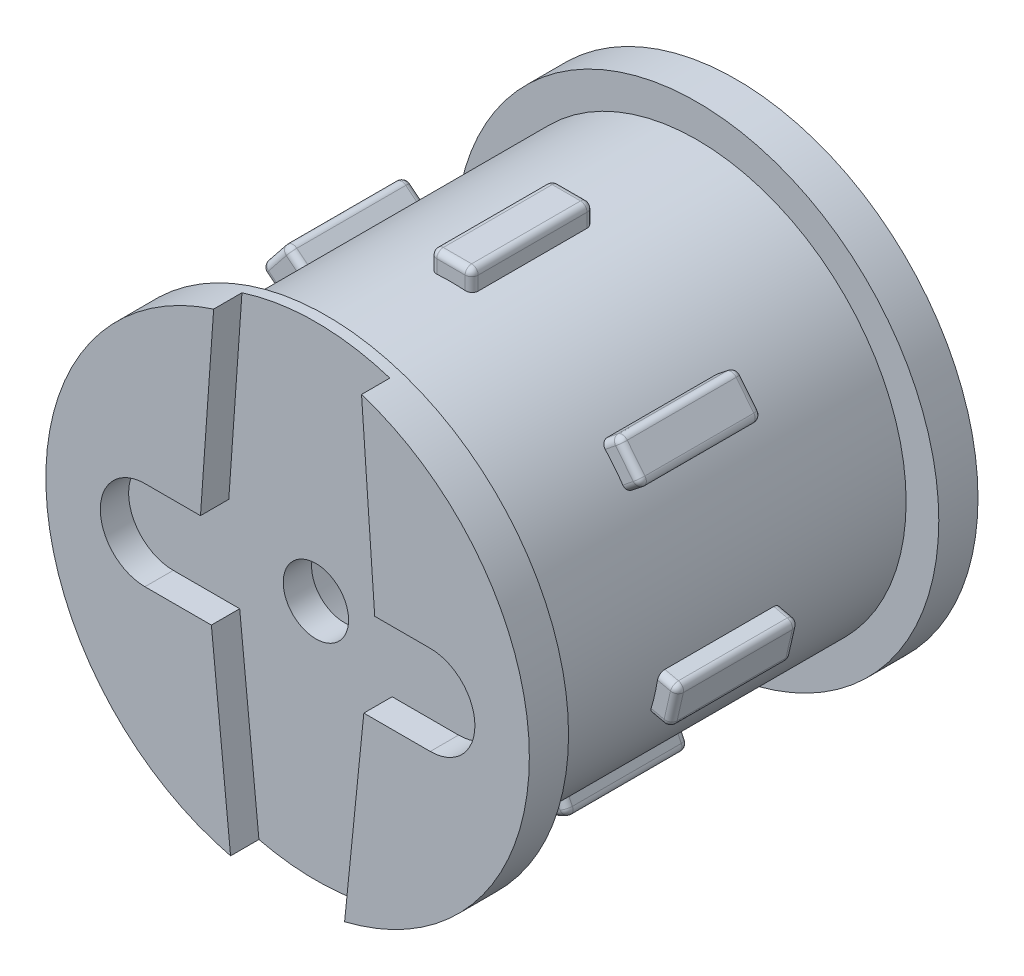
SolidWorks part; units mm, degrees
ref_plane "Ebene vorne" through (0, 0, 0) normal (0, 0, 1) x (1, 0, 0)
ref_plane "Ebene oben" through (0, 0, 0) normal (0, 1, 0) x (1, 0, 0)
ref_plane "Ebene rechts" through (0, 0, 0) normal (1, 0, 0) x (0, 0, -1)
sketch "Skizze1" plane through (0, 0, 0) normal (0, 0, 1) x (1, 0, 0)
  circle A0 centre (0, 0) radius 9.6
  dimension "D1" = 19.2
extrude "Aufsatz-Linear austragen1" add sketch "Skizze1" along normal blind 10.3 and the other way blind 10.3
ref_axis "Rotationsachse" through (0, 0, -10.3) along (0, 0, 1)
sketch "Skizze2" plane through (0, 0, 10.3) normal (0, 0, 1) x (1, 0, 0)
  circle A0 centre (0, 0) radius 11.1
  dimension "D1" = 22.2
extrude "Aufsatz-Linear austragen2" add sketch "Skizze2" against normal blind 1.8
sketch "Skizze3" plane through (0, 0, -10.3) normal (0, 0, -1) x (-1, 0, 0)
  circle A0 centre (0, 0) radius 11.1
  dimension "D1" = 22.2
extrude "Aufsatz-Linear austragen3" add sketch "Skizze3" against normal blind 1.8
sketch "Skizze12" plane through (0, 0, 10.3) normal (0, 0, 1) x (1, 0, 0)
  line L0 (1.9899, -17.001) -> (3.5, -2.05)
  line L1 (-3.05, 2.05) -> (3.05, 2.05)
  line L2 (-3.05, 2.05) -> (-3.05, -2.05)
  line L3 (-3.05, -2.05) -> (3.05, -2.05)
  line L4 (3.05, 2.05) -> (3.05, -2.05)
  line L5 (-3.05, 2.05) -> (3.05, -2.05) construction
  line L6 (-3.05, -2.05) -> (3.05, 2.05) construction
  line L7 (3.05, 2.05) -> (6.55, 2.05)
  line L8 (3.05, 2.05) -> (3.05, -2.05)
  line L9 (3.05, -2.05) -> (6.55, -2.05)
  line L10 (6.55, 2.05) -> (6.55, -2.05)
  line L11 (-3.05, -2.05) -> (-3.5, -2.05)
  line L12 (-1.9899, -17.001) -> (-3.5, -2.05)
  line L13 (4, 2.05) -> (2.7431, 19.7448)
  line L14 (-4, 2.05) -> (-2.7431, 19.7448)
  line L16 (-3.05, -2.05) -> (-6.55, -2.05)
  line L17 (-3.05, -2.05) -> (-3.05, 2.05)
  line L18 (-3.05, 2.05) -> (-6.55, 2.05)
  line L19 (-6.55, -2.05) -> (-6.55, 2.05)
  circle A0 centre (6.55, 0) radius 2.05
  circle A1 centre (0, -16.8) radius 2
  circle A2 centre (0, 19.55) radius 2.75
  circle A3 centre (-6.55, 0) radius 2.05
  point P0 (0, 0)
  point P12 (0, -2.05)
  circle M11 centre (0, 0) radius 11.1
  dimension "D5" = 4
  dimension "D9" = 17.5
  dimension "D13" = 5.5
  dimension "D6" = 4.1
  dimension "D2" = 4.1
  dimension "D1" = 6.1
  dimension "D3" = 3.5
  dimension "D4" = 14.75
  dimension "D7" = 3.5
  dimension "D8" = 3.5
  dimension "D10" = 4
  dimension "D11" = 4
  dimension "D12" = 3.5
extrude "Schnitt-Linear austragen1" cut sketch "Skizze12" against normal blind 1.3 contours A1 M11 | L11 L9 L3 M11 | L4 L1 L2 L3 | A0 L7 L4 L9 | L10 A0 | L10 A0 | L18 L1 L7 L13 L14 M11 | A2 L14 L13 M11 | L17 L16 L19 L18 | A3 | A2 | L2 L1 L4 L3 region at (0, -13.1061, 10.3) region at (0, -6.3029, 10.3) region at (4.0504, 0, 10.3) region at (0, 0, 10.3) region at (5.68, 0, 10.3) region at (7.42, 0, 10.3) region at (0, 6.3626, 10.3) region at (0, 14.1384, 10.3)
sketch "Skizze8" plane through (0, 0, 0) normal (1, 0, 0) x (0, 0, -1)
  line L0 (10.3, 0) -> (10.3, 8)
  line L1 (10.3, -11.1) -> (10.3, 11.1) construction
  line L2 (10.3, 8) -> (8.5, 8)
  line L3 (8.5, 11.1) -> (8.5, -11.1) construction
  line L4 (8.5, 8) -> (-7.7, 3.5)
  line L6 (-7.7, 3.5) -> (-7.7, 0)
  line L7 (-7.7, 0) -> (10.3, 0)
  dimension "D1" = 8
  dimension "D2" = 3.5
  dimension "D3" = 18
revolve "Schnitt-Rotation1" cut sketch "Skizze8" angle 360 about axis through (0, 0, -10.3) along (0, 0, 1)
ref_plane "Schnittebene_Zaehne" through (0, 0, 0) normal (0, 0, -1) x (-1, 0, 0)
sketch "Skizze11" plane through (0, 0, 0) normal (0, 0, -1) x (-1, 0, 0)
  line L0 (0, 0) -> (0, 12.664) construction
  line L6 (-0.95, 8.71) -> (0.95, 8.71)
  line L7 (-0.95, 8.71) -> (-0.95, 10.49)
  line L8 (-0.95, 10.49) -> (0.95, 10.49)
  line L9 (0.95, 8.71) -> (0.95, 10.49)
  line L10 (-0.95, 8.71) -> (0.95, 10.49) construction
  line L11 (-0.95, 10.49) -> (0.95, 8.71) construction
  circle A1 centre (0, 0) radius 9.6 construction
  point P3 (0, 9.6)
  dimension "D1" = 0.89
  dimension "D2" = 1.9
extrude "Aufsatz-Linear austragen4" add sketch "Skizze11" along normal blind 2.8 and the other way blind 2.8
pattern_circular "Kreismuster2" count 7 over 360 about axis through (0, 0, -10.3) along (0, 0, 1) of "Aufsatz-Linear austragen4"
fillet "Verrundung1" radius 0.3 56 edges at (8.2014, 6.5404, 2.8) (7.6091, 7.2831, 0) (8.2014, 6.5404, -2.8) (8.7937, 5.7977, 0) (-8.4274, 5.5055, 2.8) (-7.2428, 6.991, 2.8) (-7.2428, 6.991, -2.8) (-8.4274, 5.5055, -2.8) (-9.5588, -3.1562, -2.8) (-9.9816, -1.3038, -2.8) (-9.5588, -3.1562, 2.8) (-9.9816, -1.3038, 2.8) (-5.2041, -8.6168, -2.8) (-3.4922, -9.4412, -2.8) (-3.4922, -9.4412, 2.8) (-5.2041, -8.6168, 2.8) (5.2041, -8.6168, 2.8) (3.4922, -9.4412, 2.8) (3.4922, -9.4412, -2.8) (5.2041, -8.6168, -2.8) (9.5588, -3.1562, 2.8) (9.5588, -3.1562, -2.8) (9.9816, -1.3038, 2.8) (9.9816, -1.3038, -2.8) (8.4274, 5.5055, 2.8) (8.4274, 5.5055, -2.8) (7.2428, 6.991, -2.8) (7.2428, 6.991, 2.8) (0.95, 10.0214, 2.8) (0.95, 10.0214, -2.8) (-0.95, 10.0214, -2.8) (-0.95, 10.0214, 2.8) (10.4384, -1.4081, 0) (10.227, -2.3342, 2.8) (10.227, -2.3342, -2.8) (10.0156, -3.2604, 0) (4.5514, -9.4512, 2.8) (4.5514, -9.4512, -2.8) (5.4074, -9.039, 0) (3.6955, -9.8634, 0) (-4.5514, -9.4512, 2.8) (-4.5514, -9.4512, -2.8) (-5.4074, -9.039, 0) (-3.6955, -9.8634, 0) (-10.227, -2.3342, 2.8) (-10.227, -2.3342, -2.8) (-10.0156, -3.2604, 0) (-10.4384, -1.4081, 0) (-8.2014, 6.5404, -2.8) (-8.2014, 6.5404, 2.8) (-8.7937, 5.7977, 0) (-7.6091, 7.2831, 0) (0, 10.49, -2.8) (0, 10.49, 2.8) (0.95, 10.49, 0) (-0.95, 10.49, 0)
sketch "Skizze14" plane through (0, 0, 10.3) normal (0, 0, 1) x (1, 0, 0)
  circle A0 centre (0, 0) radius 1.5
  dimension "D1" = 3
extrude "Schnitt-Linear austragen2" cut sketch "Skizze14" against normal up to surface (2.6 mm away) up to face at (-3.5, 0, 7.7)
